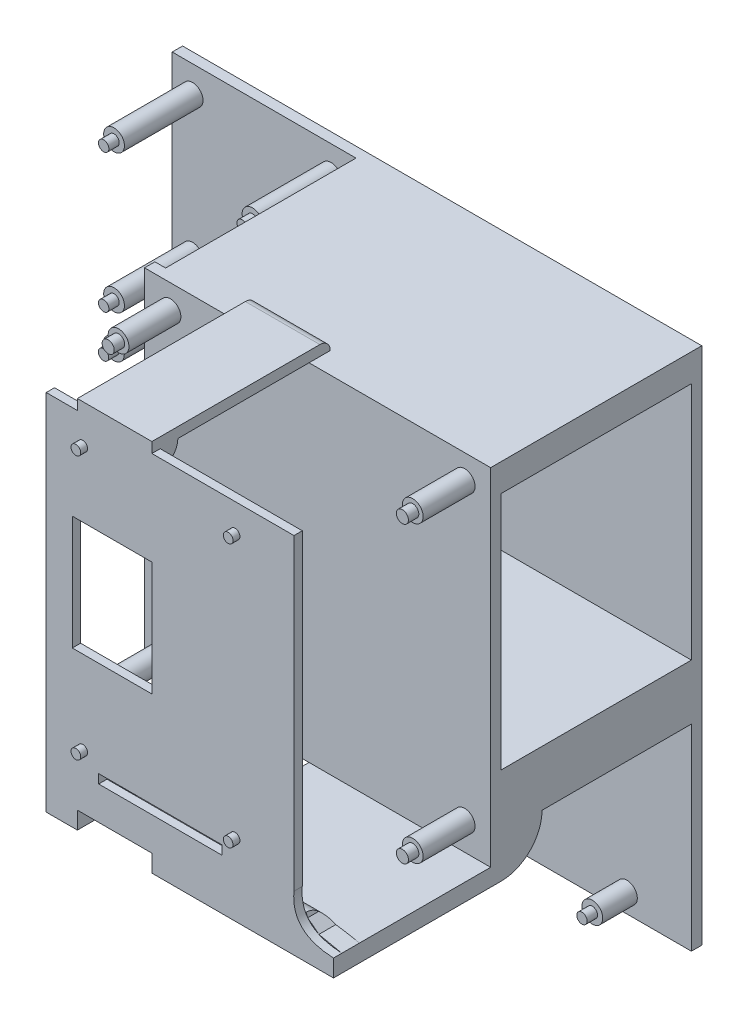
SolidWorks part; units mm, degrees
note: The reader was unsure of these and kept them because the rebuilt part matched: shared geometry of "Sketch24<2>", "Sketch31<3>", "Sketch15<3>", "Sketch27<3>".
ref_plane "Front" through (0, 0, 0) normal (0, 0, 1) x (1, 0, 0)
ref_plane "Top" through (0, 0, 0) normal (0, 1, 0) x (1, 0, 0)
ref_plane "Right" through (0, 0, 0) normal (1, 0, 0) x (0, 0, -1)
sketch "Sketch1" plane through (0, 0, 0) normal (0, 0, 1) x (1, 0, 0)
  line L32 (46.156, 71.9617) -> (196.156, 71.9617)
  line L33 (46.156, 71.9617) -> (46.156, 221.9617)
  line L34 (46.156, 221.9617) -> (196.156, 221.9617)
  line L35 (196.156, 71.9617) -> (196.156, 221.9617)
  circle A16 centre (100.2373, 119.2222) radius 1.6031
  circle A17 centre (100.2373, 77.4222) radius 1.597
  circle A18 centre (177.5373, 77.4222) radius 1.6008
  circle A19 centre (177.5373, 119.2222) radius 1.6046
  circle A20 centre (103.616, 218.7617) radius 1.7523
  circle A21 centre (103.616, 133.7622) radius 1.7492
  circle A22 centre (188.616, 133.7617) radius 1.752
  circle A23 centre (188.616, 218.7617) radius 1.7473
  circle A24 centre (51.9595, 119.6216) radius 1.5958
  circle A25 centre (91.9595, 119.6216) radius 1.603
  circle A26 centre (91.9595, 79.6216) radius 1.6022
  circle A27 centre (51.9595, 79.6216) radius 1.6042
  circle A28 centre (52.007, 171.906) radius 1.5958
  circle A29 centre (92.007, 171.906) radius 1.603
  circle A30 centre (92.007, 131.906) radius 1.6022
  circle A31 centre (52.007, 131.906) radius 1.6042
  dimension "D2" = 3.2
  dimension "D3" = 3.2
  dimension "D4" = 88.1995
  dimension "D5" = 88.2
  dimension "D8" = 7.54
  dimension "D9" = 7.54
  dimension "D10" = 92.54
  dimension "D11" = 92.54
  dimension "D1" = 150
  dimension "D7" = 150
extrude "Boss-Extrude2" add sketch "Sketch1" along normal blind 3 contours L34 L35 L32 L33
sketch "Sketch7" plane through (0, 0, 0) normal (0, 0, 1) x (1, 0, 0)
  circle A16 centre (100.2373, 119.2222) radius 1.6031
  circle A17 centre (100.2373, 77.4222) radius 1.597
  circle A18 centre (177.5373, 77.4222) radius 1.6008
  circle A19 centre (177.5373, 119.2222) radius 1.6046
  circle A38 centre (100.2373, 77.4222) radius 3
  circle A39 centre (177.5373, 77.4222) radius 3
  circle A41 centre (177.5373, 119.2222) radius 3
  circle A42 centre (100.2373, 119.2222) radius 3
extrude "Boss-Extrude3" add sketch "Sketch7" along normal blind 13
sketch "Sketch13" plane through (0, 0, 3) normal (0, 0, 1) x (1, 0, 0)
  line L4 (196.156, 71.9617) -> (196.156, 221.9617) construction
  line L5 (196.156, 221.9617) -> (99.2532, 221.9617)
  line L6 (196.156, 221.9617) -> (196.156, 213.9644)
  line L7 (196.156, 213.9644) -> (99.2532, 213.9644)
  line L8 (99.2532, 221.9617) -> (99.2532, 213.9644)
  line L9 (99.2532, 213.9644) -> (107.2532, 213.9644)
  line L10 (99.2532, 213.9644) -> (99.2532, 126.6541)
  line L11 (99.2532, 126.6541) -> (107.2532, 126.6541)
  line L12 (107.2532, 213.9644) -> (107.2532, 126.6541)
  line L13 (196.156, 128.8064) -> (181.0099, 128.8064)
  line L14 (196.156, 128.8064) -> (196.156, 136.8064)
  line L15 (196.156, 136.8064) -> (181.0099, 136.8064)
  line L16 (181.0099, 128.8064) -> (181.0099, 136.8064)
  line L18 (196.156, 136.8064) -> (107.2532, 136.8064)
  line L19 (196.156, 136.8064) -> (196.156, 144.8064)
  line L20 (196.156, 144.8064) -> (107.2532, 144.8064)
  line L21 (107.2532, 136.8064) -> (107.2532, 144.8064)
  line M32 (196.156, 71.9617) -> (196.156, 221.9617)
  line M33 (196.156, 221.9617) -> (46.156, 221.9617)
  dimension "D4" = 8
  dimension "D1" = 7.9973
  dimension "D2" = 8
  dimension "D3" = 8
extrude "Boss-Extrude4" add sketch "Sketch13" along normal blind 55 contours L8 L7 M33 M32 | L12 L7 L10 L11 | L20 L12 L18 L15 M32 | L16 L13 L15 M32
sketch "Sketch14" plane through (0, 0, 58) normal (0, 0, 1) x (1, 0, 0)
  line L17 (96.156, 121.9617) -> (196.156, 121.9617)
  line L18 (96.156, 121.9617) -> (96.156, 221.9617)
  line L19 (96.156, 221.9617) -> (196.156, 221.9617)
  line L20 (196.156, 121.9617) -> (196.156, 221.9617)
extrude "Boss-Extrude5" add sketch "Sketch14" along normal blind 3
sketch "Sketch15" plane through (0, 0, 61) normal (0, 0, 1) x (1, 0, 0)
  circle A4 centre (103.656, 214.9617) radius 3.0018
  circle A5 centre (103.656, 129.9617) radius 3.0014
  circle A6 centre (188.656, 129.9617) radius 3.0003
  circle A7 centre (188.656, 214.9617) radius 2.999
  circle A12 centre (103.656, 214.9617) radius 3.0018
  circle A13 centre (103.656, 129.9617) radius 3.0014
  circle A14 centre (188.656, 129.9617) radius 3.0003
  circle A15 centre (188.656, 214.9617) radius 2.999
  circle A24 centre (103.656, 214.9617) radius 1.7523
  circle A25 centre (103.656, 129.9617) radius 1.7492
  circle A26 centre (188.656, 129.9617) radius 1.752
  circle A27 centre (188.656, 214.9617) radius 1.7473
  point P8 (103.656, 217.9635)
  point P9 (105.0847, 217.6017)
  point P10 (191.6551, 214.9617)
  point P15 (106.6574, 129.9617)
  point P16 (191.1117, 216.6834)
  point P17 (103.656, 131.3481)
  point P18 (0, 0)
  point P19 (191.6564, 129.9617)
  point P20 (185.6557, 129.9617)
sketch "Sketch17" plane through (0, 0, 13) normal (0, 0, 1) x (1, 0, 0)
  circle A0 centre (100.2373, 119.2222) radius 1.5
  circle A1 centre (100.2373, 77.4222) radius 1.5
  circle A2 centre (177.5373, 77.4222) radius 1.5
  circle A3 centre (177.5373, 119.2222) radius 1.5
sketch "Sketch20" plane through (0, 0, 3) normal (0, 0, 1) x (1, 0, 0)
  circle A8 centre (92.0527, 214.2817) radius 3
  circle A9 centre (52.0527, 214.2817) radius 3
  circle A10 centre (52.0527, 174.2817) radius 3
  circle A11 centre (92.0527, 174.2817) radius 3
  circle A12 centre (92.0052, 161.9973) radius 3
  circle A13 centre (52.0052, 161.9973) radius 3
  circle A14 centre (92.0052, 121.9973) radius 3
  circle A15 centre (52.0052, 121.9973) radius 3
extrude "Boss-Extrude22" add sketch "Sketch15" along normal blind 15 contours A7 | A4 | A5 | A6
extrude "Boss-Extrude8" add sketch "Sketch20" along normal blind 22.7
sketch "Sketch21" plane through (0, 0, 25.7) normal (0, 0, 1) x (1, 0, 0)
  circle A0 centre (52.0052, 161.9973) radius 1.5
  circle A1 centre (92.0052, 161.9973) radius 1.5
  circle A2 centre (92.0052, 121.9973) radius 1.5
  circle A3 centre (52.0052, 121.9849) radius 1.5
  circle A4 centre (52.0527, 214.2817) radius 1.5
  circle A5 centre (92.0527, 214.2817) radius 1.5
  circle A6 centre (92.0527, 174.2693) radius 1.5
  circle A7 centre (52.0527, 174.2693) radius 1.5
  point P0 (0, 0)
sketch "Sketch23" plane through (0, 121.9617, 0) normal (0, -1, 0) x (1, 0, 0)
  line L0 (96.156, 61) -> (196.156, 61) construction
  line L1 (196.156, 58) -> (143.6895, 58)
  line L2 (196.156, 58) -> (196.156, 61)
  line L3 (196.156, 61) -> (143.6895, 61)
  line L4 (143.6895, 58) -> (143.6895, 61)
  line L5 (181.0099, 58) -> (107.2532, 58) construction
  line L6 (122.156, 58) -> (113.156, 58)
  line L7 (122.156, 58) -> (122.156, 61)
  line L8 (122.156, 61) -> (113.156, 61)
  line L9 (113.156, 58) -> (113.156, 61)
  line L10 (96.156, 61) -> (96.156, 58) construction
  dimension "D1" = 9
  dimension "D2" = 17
extrude "Boss-Extrude9" add sketch "Sketch23" along normal blind 5
sketch "Sketch24" plane through (196.156, 0, 0) normal (1, 0, 0) x (0, 0, -1)
  line L1 (-58, 128.8064) -> (-3, 128.8064) construction
  line L10 (0, 71.9617) -> (0, 221.9617)
  line L11 (0, 221.9617) -> (-61, 221.9617)
  line L12 (-61, 221.9617) -> (-61, 116.9617)
  line L13 (-61, 116.9617) -> (-58, 116.9617)
  line L14 (-58, 116.9617) -> (-58, 128.8064)
  line L15 (-58, 128.8064) -> (-3, 128.8064)
  line L16 (-3, 128.8064) -> (-3, 71.9617)
  line L17 (-3, 71.9617) -> (0, 71.9617)
  line L22 (-58, 116.9617) -> (-58, 128.8064)
  line L23 (-58, 128.8064) -> (-46.1553, 128.8064)
  arc A1 (-58, 116.9617) -> (-46.1553, 128.8064) centre (-58, 128.8064) ccw
  dimension "D1" = 0
extrude "Boss-Extrude10" add sketch "Sketch24" against normal blind 52.47
extrude "Boss-Extrude11" add sketch "Sketch24<2>" against normal blind 9 from offset 74 offset against normal yes
sketch "Sketch24<2>" plane through (196.156, 0, 0) normal (1, 0, 0) x (0, 0, -1) same geometry as "Sketch24"
sketch "Sketch25" plane through (0, 136.8064, 0) normal (0, -1, 0) x (1, 0, 0)
  line L1 (122.1579, 46.1623) -> (113.156, 46.1623)
  line L2 (122.1579, 46.1623) -> (122.1579, 58)
  line L3 (122.1579, 58) -> (113.156, 58)
  line L4 (113.156, 46.1623) -> (113.156, 58)
extrude "Boss-Extrude12" add sketch "Sketch25" along normal blind 8
sketch "Sketch26" plane through (0, 0, 61) normal (0, 0, 1) x (1, 0, 0)
  line L1 (122.156, 116.9617) -> (113.156, 116.9617)
  line L2 (122.156, 116.9617) -> (122.156, 121.9617)
  line L3 (122.156, 121.9617) -> (113.156, 121.9617)
  line L4 (113.156, 116.9617) -> (113.156, 121.9617)
  line L5 (143.6895, 121.9617) -> (196.156, 121.9617)
  line L6 (143.6895, 121.9617) -> (143.6895, 116.9617)
  line L7 (143.6895, 116.9617) -> (196.156, 116.9617)
  line L8 (196.156, 121.9617) -> (196.156, 116.9617)
extrude "Boss-Extrude13" add sketch "Sketch26" along normal blind 43
sketch "Sketch27" plane through (0, 0, 104) normal (0, 0, 1) x (1, 0, 0)
  line L0 (113.156, 116.9617) -> (122.156, 116.9617) construction
  line L1 (113.156, 116.9617) -> (196.156, 116.9617)
  line L2 (113.156, 116.9617) -> (113.156, 221.9617)
  line L3 (113.156, 221.9617) -> (196.156, 221.9617)
  line L4 (196.156, 116.9617) -> (196.156, 221.9617)
  line L5 (184.7289, 132.9621) -> (184.7289, 221.9617)
  line L6 (122.156, 121.9617) -> (143.6895, 121.9617)
  line L7 (122.156, 121.9617) -> (122.156, 116.9617)
  line L8 (122.156, 116.9617) -> (143.6895, 116.9617)
  line L9 (143.6895, 121.9617) -> (143.6895, 116.9617)
  line L15 (128.306, 131.5774) -> (164.006, 131.5774)
  line L16 (128.306, 131.5774) -> (128.306, 134.1774)
  line L17 (128.306, 134.1774) -> (164.006, 134.1774)
  line L18 (164.006, 131.5774) -> (164.006, 134.1774)
  line L22 (120.6895, 161.7974) -> (143.6895, 161.7974)
  line L23 (143.6895, 161.7974) -> (143.6895, 194.7974)
  line L24 (143.6895, 194.7974) -> (120.6895, 194.7974)
  line L25 (120.6895, 194.7974) -> (120.6895, 161.7974)
  circle A2 centre (167.7221, 137.7974) radius 1.4
  circle A3 centre (123.7221, 137.7974) radius 1.4
  circle A4 centre (123.7221, 213.8783) radius 1.4
  circle A5 centre (167.7221, 213.8783) radius 1.4
  spline S0 degree 2 poles (196.156, 121.9617) (183.8022, 122.5197) (184.7289, 132.9621) knots 0 0 0 1 1 1
  line M22 (143.6895, 121.9617) -> (143.6895, 116.9617)
  line M23 (143.6895, 116.9617) -> (196.156, 116.9617)
  line M24 (196.156, 116.9617) -> (196.156, 121.9617)
  line M25 (196.156, 121.9617) -> (143.6895, 121.9617)
  dimension "D2" = 24
  dimension "D4" = 23
  dimension "D1" = 71.5729
  dimension "D3" = 33
extrude "Boss-Extrude14" add sketch "Sketch27" along normal blind 2.4 contours M25 M22 M23 M24 | S0 L5 L3 L2 L1 L7 L6 A5 A4 A3 A2 L18 L15 L16 L17 M25
sketch "Sketch29" plane through (0, 221.9617, 0) normal (0, 1, 0) x (1, 0, 0)
  line L1 (143.686, -106.4) -> (122.156, -106.4)
  line L2 (143.686, -106.4) -> (143.686, -57.8685)
  line L3 (143.686, -57.8685) -> (122.156, -57.8685)
  line L4 (122.156, -106.4) -> (122.156, -57.8685)
  line L5 (96.156, -58) -> (196.156, -58)
  line L8 (196.156, -104) -> (196.156, -61) construction
  dimension "D1" = 52.47
  dimension "D2" = 21.53
extrude "Boss-Extrude15" add sketch "Sketch29" along normal blind 3 contours L4 L3 L2 L1
sketch "Sketch30" plane through (122.156, 0, 0) normal (-1, 0, 0) x (0, 0, 1)
  line L0 (106.4, 224.9617) -> (57.8685, 224.9617) construction
  line L1 (57.8685, 224.9617) -> (57.8685, 221.9617) construction
  line L2 (57.8685, 224.9617) -> (57.8685, 221.9617)
  line L3 (57.8685, 221.9617) -> (54.8685, 221.9617)
  arc A0 (57.8685, 224.9617) -> (54.8685, 221.9617) centre (57.8685, 221.9617) ccw
extrude "Boss-Extrude16" add sketch "Sketch30" against normal blind 21.53
sketch "Sketch31" plane through (113.156, 0, 0) normal (-1, 0, 0) x (0, 0, 1)
  line L0 (104, 121.9617) -> (104, 221.9617) construction
  line L1 (104, 121.9617) -> (61, 121.9617) construction
  line L2 (104, 121.9617) -> (98.9057, 121.9617)
  line L3 (104, 127.056) -> (104, 121.9617)
  arc A0 (104, 127.056) -> (98.9057, 121.9617) centre (104, 121.9617) ccw
  dimension "D1" = 5.0943
sketch "Sketch32" plane through (122.156, 0, 0) normal (-1, 0, 0) x (0, 0, 1)
  line L0 (104, 121.9617) -> (104, 221.9617) construction
  line L1 (104, 221.9617) -> (61, 221.9617) construction
  line L2 (104, 221.9617) -> (104, 216.871)
  line L3 (98.9093, 221.9617) -> (104, 221.9617)
  arc A0 (104, 216.871) -> (98.9093, 221.9617) centre (104, 221.9617) cw
extrude "Boss-Extrude17" add sketch "Sketch31" against normal blind 9
extrude "Boss-Extrude18" add sketch "Sketch31<3>" against normal blind 52.47 from offset 30.53 offset against normal yes
sketch "Sketch31<3>" plane through (113.156, 0, 0) normal (-1, 0, 0) x (0, 0, 1) same geometry as "Sketch31"
sketch "Sketch33" plane through (0, 0, 104) normal (0, 0, 1) x (1, 0, 0)
  line L0 (196.156, 121.9617) -> (189.5285, 123.3686)
  line L1 (189.5285, 123.3686) -> (186.3072, 125.9152)
  line L2 (186.3072, 125.9152) -> (185.7971, 127.056)
  line L3 (196.156, 127.056) -> (185.6078, 127.056) construction
  line L4 (185.7971, 127.056) -> (196.156, 127.056)
  line L5 (196.156, 127.056) -> (196.156, 121.9617)
  parabola Q3 (196.156, 121.9617) -> (184.7289, 132.9621) focus (189.2731, 128.1226) apex (186.3072, 125.9152) construction
  parabola Q4 (196.156, 121.9617) -> (185.6078, 127.056) focus (189.2731, 128.1226) apex (186.3072, 125.9152) construction
  parabola Q5 (196.156, 121.9617) -> (184.7289, 132.9621) focus (189.2731, 128.1226) apex (186.3072, 125.9152) construction
extrude "Cut-Extrude5" cut sketch "Sketch33" against normal blind 8
extrude "Boss-Extrude19" add sketch "Sketch32" against normal blind 21.53
extrude "Boss-Extrude20" add sketch "Sketch21" along normal blind 3
extrude "Boss-Extrude21" add sketch "Sketch17" along normal blind 3
extrude "Boss-Extrude23" add sketch "Sketch15<3>" along normal blind 18 contours A25 | A24 | A27 | A26
sketch "Sketch15<3>" plane through (0, 0, 61) normal (0, 0, 1) x (1, 0, 0) same geometry as "Sketch15"
extrude "Boss-Extrude24" add sketch "Sketch27<3>" along normal blind 4.4 contours A2 | A3 | A4 | A5
sketch "Sketch27<3>" plane through (0, 0, 104) normal (0, 0, 1) x (1, 0, 0) same geometry as "Sketch27"
